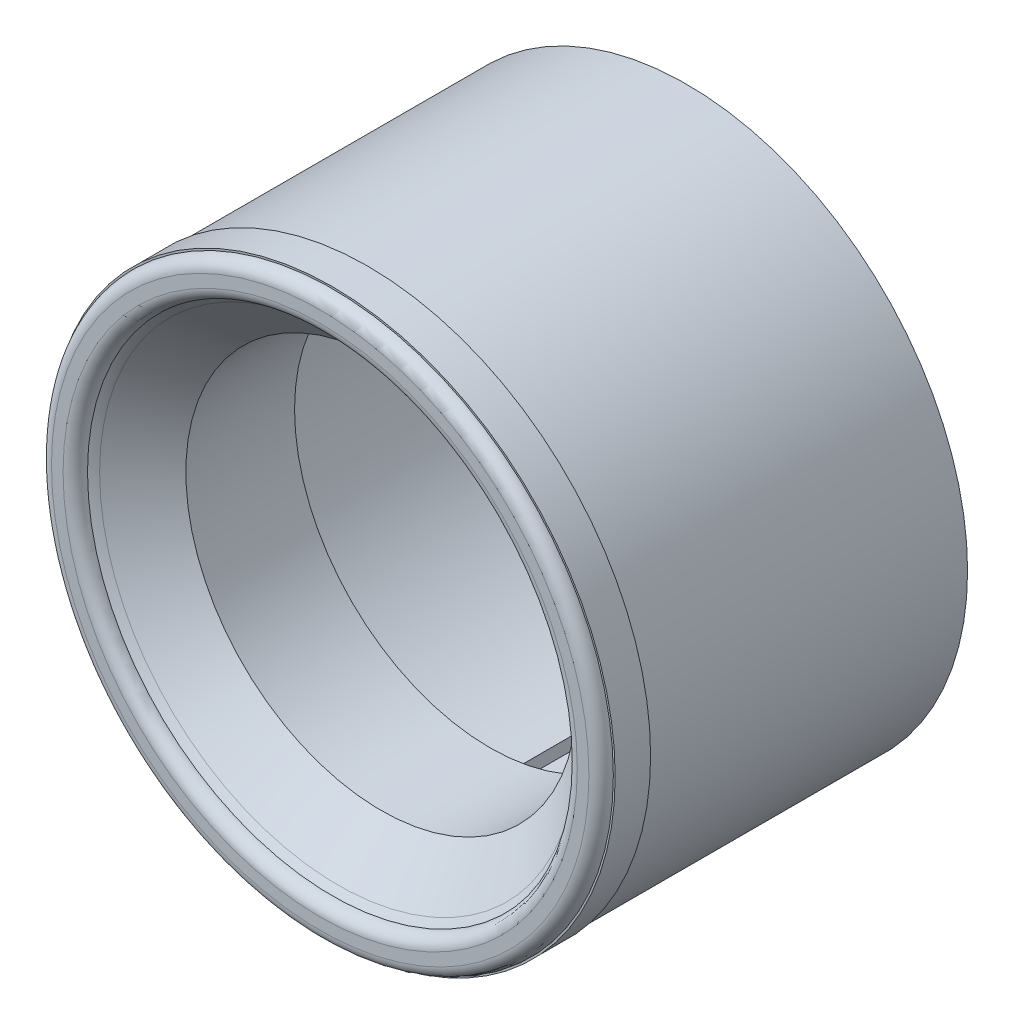
SolidWorks part; units mm, degrees
ref_plane "정면" through (0, 0, 0) normal (0, 0, 1) x (1, 0, 0)
ref_plane "윗면" through (0, 0, 0) normal (0, 1, 0) x (1, 0, 0)
ref_plane "우측면" through (0, 0, 0) normal (1, 0, 0) x (0, 0, -1)
sketch "스케치1" plane through (0, 0, 0) normal (0, 0, 1) x (1, 0, 0)
  circle A0 centre (0, 0) radius 23
  circle A1 centre (0, 0) radius 20.05
  dimension "D1" = 46
  dimension "D2" = 40.1
extrude "보스-돌출1" add sketch "스케치1" along normal blind 30
fillet "필렛1" radius 1 2 edges at (20.05, 0, 30) (23, 0, 30)
chamfer "모따기1" distance 0.5 angle 45 1 edges at (20.05, 0, 0)
sketch "스케치2" plane through (0, 0, 0) normal (0, 0, 1) x (1, 0, 0)
  line L0 (0, 0) -> (0, -20.05) construction
  line L1 (-1.5, -19.05) -> (1.5, -19.05)
  line L2 (-1.5, -19.05) -> (-1.5, -21.05)
  line L3 (-1.5, -21.05) -> (1.5, -21.05)
  line L4 (1.5, -19.05) -> (1.5, -21.05)
  line L5 (-1.5, -19.05) -> (1.5, -21.05) construction
  line L6 (-1.5, -21.05) -> (1.5, -19.05) construction
  circle A0 centre (0, 0) radius 20.05 construction
  point P0 (0, -20.05)
  dimension "D1" = 3
  dimension "D2" = 2
extrude "컷-돌출1" cut sketch "스케치2" along normal blind 25
chamfer "모따기2" distance 1 angle 45 1 edges at (0, -20.05, 25)
ref_plane "평면1" through (0, 0, 29) normal (0, 0, 1) x (1, 0, 0)
sketch "스케치3" plane through (0, 0, 29) normal (0, 0, 1) x (1, 0, 0)
  circle A0 centre (0, 0) radius 23.15
  circle A1 centre (0, 0) radius 16
  dimension "D1" = 46.3
  dimension "D2" = 32
extrude "보스-돌출2" add sketch "스케치3" against normal blind 2.9
sketch "스케치4" plane through (0, 0, 26.1) normal (0, 0, -1) x (-1, 0, 0)
  circle A0 centre (0, 0) radius 17.425
  circle A1 centre (0, 0) radius 16
  dimension "D1" = 34.85
extrude "보스-돌출3" add sketch "스케치4" along normal blind 10
chamfer "모따기4" distance 4 angle 45 1 edges at (16, 0, 29)
fillet "필렛3" radius 7 1 edges at (20, 0, 29)
